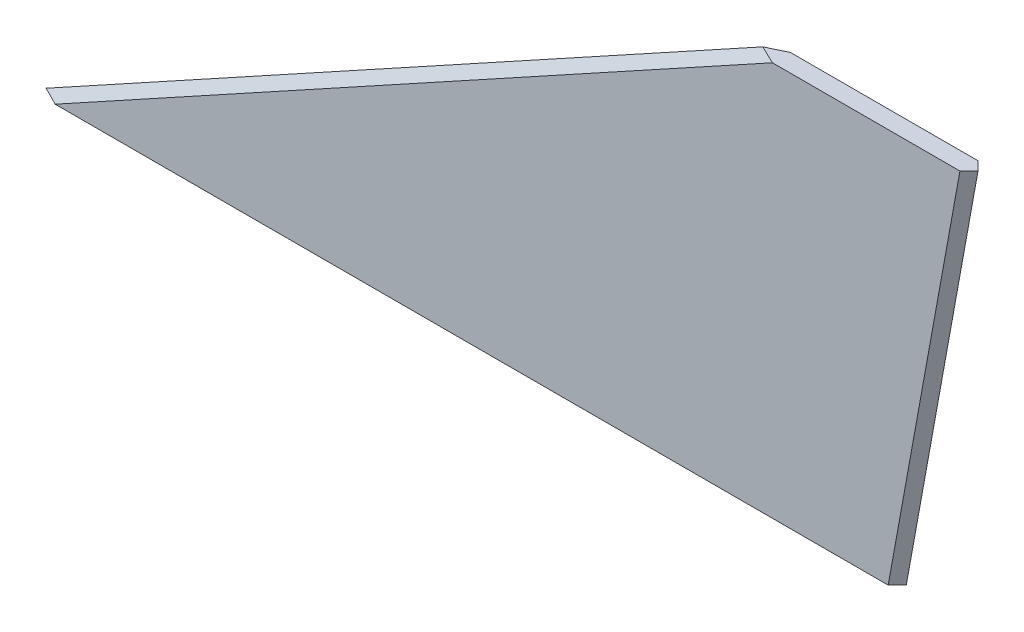
SolidWorks part; units mm, degrees
material "S-Glass Fiber"
ref_plane "Front Plane" through (0, 0, 0) normal (0, 0, 1) x (1, 0, 0)
ref_plane "Top Plane" through (0, 0, 0) normal (0, 1, 0) x (1, 0, 0)
ref_plane "Right Plane" through (0, 0, 0) normal (1, 0, 0) x (0, 0, -1)
sketch "Sketch1" plane through (0, 0, 0) normal (0, 0, 1) x (1, 0, 0)
  line L0 (0, 0) -> (304.8, 0)
  line L1 (254, 0) -> (254, 139.7) construction
  line L2 (0, 0) -> (254, 139.7)
  line L3 (254, 139.7) -> (330.2, 139.7)
  line L4 (304.8, 0) -> (330.2, 139.7)
  point P3 (254, 0)
  dimension "D1" = 304.8
  dimension "D2" = 254
  dimension "D3" = 139.7
  dimension "D4" = 76.2
extrude "Boss-Extrude1" add sketch "Sketch1" along normal blind 6.35 contours L2 L0 L1 | L0 L4 L3 L1 region at (169.3333, 46.5667, 0) region at (286.1733, 74.5067, 0)
chamfer "Chamfer1" distance 3.175 distance2 3.175 4 edges at (317.5, 69.85, 0) (317.5, 69.85, 6.35) (127, 69.85, 6.35) (127, 69.85, 0)
sketch "Sketch2" plane through (0, 0, 0) normal (1, 0, 0) x (0, 0, -1)
  circle A0 centre (-3.175, -50.7007) radius 50.8
  dimension "D3" = 101.6
  dimension "D1" = 50.8
  dimension "D2" = 50.8
extrude "Cut-Extrude1" cut sketch "Sketch2" along normal blind 316.484 and the other way blind 13.716
